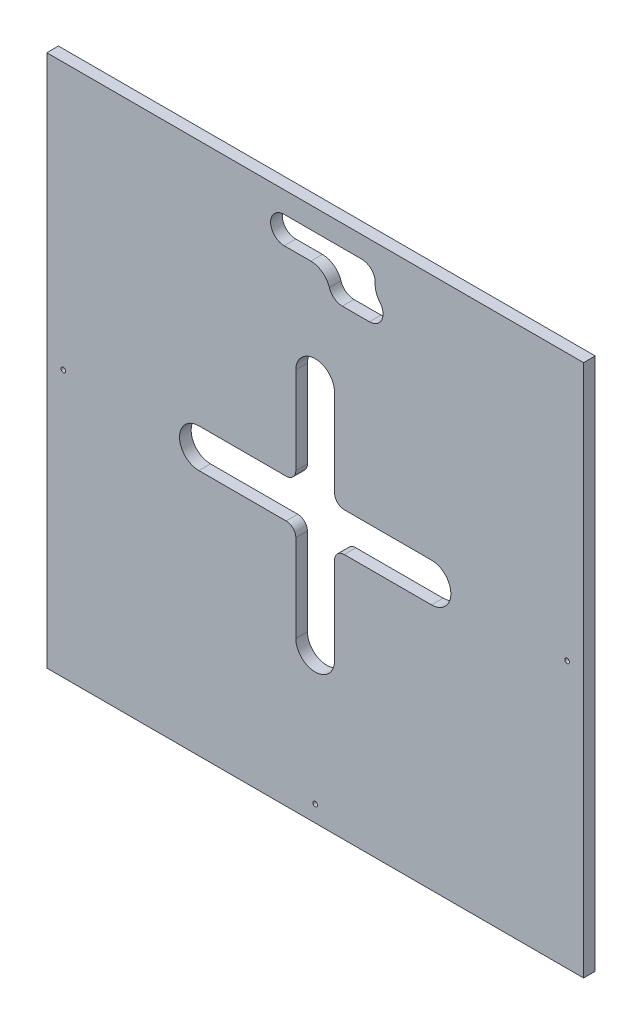
SolidWorks part; units mm, degrees
note: '?' marks a value the reader was unsure of. The reader was unsure of these and kept them because the rebuilt part matched: thickness of "Brida base1", "Chapa metálica12", "Chapa metálica15", "Chapa metálica16", "Chapa metálica17", "Chapa metálica18", "Chapa metálica19", "Chapa metálica20".
ref_plane "Alzado" through (0, 0, 0) normal (0, 0, 1) x (1, 0, 0)
ref_plane "Planta" through (0, 0, 0) normal (0, 1, 0) x (1, 0, 0)
ref_plane "Vista lateral" through (0, 0, 0) normal (1, 0, 0) x (0, 0, -1)
sketch "Croquis1" plane through (0, 0, 0) normal (0, 0, 1) x (1, 0, 0)
  line L1 (-138.5, 137.5) -> (138.5, 137.5)
  line L2 (-138.5, 137.5) -> (-138.5, -137.5)
  line L3 (-138.5, -137.5) -> (138.5, -137.5)
  line L4 (138.5, 137.5) -> (138.5, -137.5)
  line L5 (-138.5, 137.5) -> (138.5, -137.5) construction
  line L6 (-138.5, -137.5) -> (138.5, 137.5) construction
  point P0 (0, 0)
  dimension "D1" = 275
  dimension "D2" = 277
base flange "Brida base1" sketch "Croquis1" thickness 6 reverse thickness direction no parameters "D1"=0.7366
sketch "Croquis5" plane through (0, 0, -6) normal (0, 0, -1) x (-1, 0, 0)
  line L0 (122.5, 81.5) -> (122.5, 121.5) construction
  line L1 (115.5, 81.5) -> (115.5, 121.5)
  line L2 (129.5, 81.5) -> (129.5, 121.5)
  line L3 (138.5, 137.5) -> (138.5, -137.5) construction
  line L4 (110.5, 111.5) -> (110.5, 125.5) construction
  line L5 (103.5, 111.5) -> (103.5, 125.5)
  line L6 (117.5, 111.5) -> (117.5, 125.5)
  arc A0 (115.5, 81.5) -> (129.5, 81.5) centre (122.5, 81.5) ccw
  arc A1 (129.5, 121.5) -> (115.5, 121.5) centre (122.5, 121.5) ccw
  arc A2 (103.5, 111.5) -> (117.5, 111.5) centre (110.5, 111.5) ccw
  arc A3 (117.5, 125.5) -> (103.5, 125.5) centre (110.5, 125.5) ccw
  point P2 (122.5, 101.5)
  point P12 (110.5, 118.5)
  dimension "D2" = 7
  dimension "D5" = 7
  dimension "D1" = 16
  dimension "D3" = 40
  dimension "D4" = 36
  dimension "D6" = 12
  dimension "D7" = 17
  dimension "D8" = 14
extrude "Cortar-Extruir3" [suppressed] cut sketch "Croquis5" against normal through all both and the other way through all contours L6 A3 L5 A2 L1
fillet "Redondeo1" [suppressed] radius 10
sketch "Croquis6" plane through (0, 0, -6) normal (0, 0, -1) x (-1, 0, 0)
  line L0 (16, 119.5) -> (-24, 119.5) construction
  line L1 (16, 112.5) -> (-24, 112.5)
  line L2 (16, 126.5) -> (-24, 126.5)
  line L3 (-14, 107.5) -> (-28, 107.5) construction
  line L4 (-14, 100.5) -> (-28, 100.5)
  line L5 (-14, 114.5) -> (-28, 114.5)
  line L6 (-138.5, 137.5) -> (138.5, 137.5) construction
  arc A0 (16, 112.5) -> (16, 126.5) centre (16, 119.5) ccw
  arc A1 (-24, 126.5) -> (-24, 112.5) centre (-24, 119.5) ccw
  arc A2 (-14, 100.5) -> (-14, 114.5) centre (-14, 107.5) ccw
  arc A3 (-28, 114.5) -> (-28, 100.5) centre (-28, 107.5) ccw
  point P2 (-4, 119.5)
  point P9 (-21, 107.5)
  dimension "D1" = 40
  dimension "D3" = 7
  dimension "D4" = 7
  dimension "D2" = 14
  dimension "D5" = 17
  dimension "D6" = 12
  dimension "D7" = 18
  dimension "D8" = 4
extrude "Cortar-Extruir4" cut sketch "Croquis6" against normal blind 10 contours A3 L5 A2 L1 A0 L2 A1 | A1 A3 L4 A2 L1 | L5 A3 A1 L1 A2 normal cut yes
fillet "Redondeo2" radius 10 2 edges at (28.846, 114.4487, -3) (9.101, 112.5, -3)
sketch "Croquis7" plane through (0, 0, -6) normal (0, 0, -1) x (-1, 0, 0)
  line L0 (-138.5, 137.5) -> (138.5, 137.5) construction
  line L1 (-130, 129) -> (130, 129) construction
  line L2 (-130, 129) -> (-130, -129) construction
  line L3 (-130, -129) -> (130, -129) construction
  line L4 (130, 129) -> (130, -129) construction
  line L5 (-130, 129) -> (130, -129) construction
  line L6 (-130, -129) -> (130, 129) construction
  line L7 (138.5, 137.5) -> (138.5, -137.5) construction
  point P0 (0, 0)
  point P10 (-130, 0)
  point P11 (130, 0)
  point P12 (0, -129)
  dimension "D1" = 8.5
  dimension "D2" = 8.5
hole_wizard "Taladro de margen para M21" positions "Croquis11" profile "Croquis12" hole size "M2" standard "DIN" end condition through all
sketch "Croquis11" plane through (0, 0, -6) normal (0, 0, -1) x (-1, 0, 0)
  point P0 (-130, 0)
  point P3 (130, 0)
  point P6 (0, -129)
sketch "Croquis12" plane through (130, 0, -6) normal (1, 0, 0) x (0, 1, 0)
  line L0 (0, 0) -> (0, 6)
  line L1 (0, 6) -> (1.2, 6)
  line L2 (1.2, 6) -> (1.2, 0)
  line L5 (1.2, 0) -> (0, 0)
  line L11 (0, -6.35) -> (0, 107.95) construction
  dimension "Diámetro de taladro hasta el siguiente" = 2.4
  dimension "Profundidad de taladro hasta el siguiente" = 6
sketch "Croquis13" [suppressed] plane through (0, 0, 0) normal (0, 0, 1) x (1, 0, 0)
  line L1 (30, 126.5) -> (-30, 126.5) construction
  line L2 (30, 126.5) -> (30, -126.5) construction
  line L3 (30, -126.5) -> (-30, -126.5) construction
  line L4 (-30, 126.5) -> (-30, -126.5) construction
  line L5 (30, 126.5) -> (-30, -126.5) construction
  line L6 (30, -126.5) -> (-30, 126.5) construction
  line L7 (127.5, -30) -> (-127.5, -30) construction
  line L8 (127.5, -30) -> (127.5, 30) construction
  line L9 (127.5, 30) -> (-127.5, 30) construction
  line L10 (-127.5, -30) -> (-127.5, 30) construction
  line L11 (127.5, -30) -> (-127.5, 30) construction
  line L12 (127.5, 30) -> (-127.5, -30) construction
  point P0 (0, 0)
  point P5 (0, -126.5)
  point P6 (30, -126.5)
  point P8 (0, 126.5)
  point P9 (-30, -126.5)
  point P10 (-30, 126.5)
  point P11 (0, 0)
  point P12 (30, 126.5)
  point P18 (127.5, -30)
  point P19 (127.5, 30)
  point P20 (-127.5, 30)
  point P21 (-127.5, -30)
  dimension "D1" = 253
  dimension "D2" = 60
  dimension "D3" = 60
  dimension "D4" = 255
hole_wizard "Avellanado para tornillo con cabeza plana avellanada de M31" [suppressed] positions "Croquis14" profile "Croquis15" countersink size "M3" standard "DIN"
sketch "Croquis14" plane through (0, 0, 0) normal (0, 0, 1) x (1, 0, 0)
  point P0 (30, -126.5)
  point P6 (-30, -126.5)
  point P9 (-30, 126.5)
  point P15 (30, 126.5)
  point P19 (127.5, -30)
  point P22 (127.5, 30)
  point P25 (-127.5, -30)
  point P28 (-127.5, 30)
sketch "Croquis15" plane through (30, -126.5, 0) normal (1, 0, 0) x (0, -1, 0)
  line L0 (0, 0) -> (0, 6)
  line L1 (0, 6) -> (1.7, 6)
  line L2 (1.7, 6) -> (1.7, 1.45)
  line L3 (1.7, 1.45) -> (3.15, 0)
  line L5 (3.15, 0) -> (0, 0)
  line L6 (-1.7, 1.45) -> (-3.15, 0) construction
  line L11 (0, -6.35) -> (0, 107.95) construction
  dimension "Diámetro de taladro hasta el siguiente" = 3.4
  dimension "Profundidad de taladro hasta el siguiente" = 6
  dimension "Diámetro de avellanado cercano" = 6.3
  dimension "Ángulo de avellanado cercano" = 90
sketch "Croquis16" plane through (0, 0, -6) normal (0, 0, -1) x (-1, 0, 0)
  line L0 (0, 60) -> (0, -60) construction
  line L1 (10, 60) -> (10, -60)
  line L2 (-10, 60) -> (-10, -60)
  arc A0 (10, 60) -> (-10, 60) centre (0, 60) ccw
  arc A1 (-10, -60) -> (10, -60) centre (0, -60) ccw
  point P2 (0, 0)
  dimension "D2" = 10
  dimension "D1" = 120
extrude "Cortar-Extruir5" cut sketch "Croquis16" against normal through all normal cut yes
ref_axis "Eje1" through (0, 0, 0.3) along (0, 0, -1)?
pattern_circular "MatrizC1" count 4 over 360 about axis through (0, 0, 0) along (0, 0, 1) of "Cortar-Extruir5"
fillet "Redondeo3" radius 5 4 edges at (-10, -10, -3) (10, 10, -3) (10, -10, -3) (-10, 10, -3)
sketch "Líneas de pliegue1" [suppressed] plane through (0, 0, 0) normal (0, 1, 0) x (1, 0, 0)
sketch "Cuadro delimitador1" [suppressed] plane through (0, 0, 0) normal (0, 1, 0) x (1, 0, 0)
sheet metal parameters "Chapa metálica12" thickness 6 parameters "D1"=0.7366, "D7"=3
flat pattern "Chapa desplegada12" [suppressed]
sketch "Líneas de pliegue2" plane through (0, 0, 0) normal (0, 1, 0) x (1, 0, 0)
sketch3d "Cuadro delimitador2" [suppressed]
  line L0 (-138.5, -137.5, 0) -> (138.5, -137.5, 0) construction
  line L1 (-138.5, 137.5, 0) -> (138.5, 137.5, 0) construction
  line L2 (-138.5, -137.5, 0) -> (-138.5, 137.5, 0) construction
  line L3 (138.5, -137.5, 0) -> (138.5, 137.5, 0) construction
sketch "Croquis7-1" [suppressed] plane through (0, 0, -6) normal (0, 0, -1) x (-1, 0, 0)
  line L0 (-138.5, 137.5) -> (138.5, 137.5)
  line L1 (-130, 129) -> (130, 129) construction
  line L2 (-130, 129) -> (-130, -129) construction
  line L3 (-130, -129) -> (130, -129) construction
  line L4 (130, 129) -> (130, -129) construction
  line L5 (-130, 129) -> (130, -129) construction
  line L6 (-130, -129) -> (130, 129) construction
  line L7 (138.5, 137.5) -> (138.5, -137.5)
  point P0 (0, 0)
  point P10 (-130, 0)
  point P11 (130, 0)
  point P12 (0, -129)
  dimension "D1" = 8.5
  dimension "D2" = 8.5
sketch "Croquis7-7" [suppressed] plane through (0, 0, -6) normal (0, 0, -1) x (-1, 0, 0)
  line L0 (-138.5, 137.5) -> (138.5, 137.5)
  line L1 (-130, 129) -> (130, 129) construction
  line L2 (-130, 129) -> (-130, -129) construction
  line L3 (-130, -129) -> (130, -129) construction
  line L4 (130, 129) -> (130, -129) construction
  line L5 (-130, 129) -> (130, -129) construction
  line L6 (-130, -129) -> (130, 129) construction
  line L7 (138.5, 137.5) -> (138.5, -137.5)
  point P0 (0, 0)
  point P10 (-130, 0)
  point P11 (130, 0)
  point P12 (0, -129)
  dimension "D1" = 8.5
  dimension "D2" = 8.5
sheet metal parameters "Chapa metálica15" thickness 6 parameters "D1"=0.7366, "D7"=3
flat pattern "Chapa desplegada12"
sketch "Líneas de pliegue2" plane through (0, 0, 0) normal (0, 1, 0) x (1, 0, 0)
sketch3d "Cuadro delimitador2" [suppressed]
  line L0 (135.5, 137.5, 0) -> (135.5, -137.5, 0) construction
  line L1 (-135.5, 137.5, 0) -> (-135.5, -137.5, 0) construction
  line L2 (135.5, 137.5, 0) -> (-135.5, 137.5, 0) construction
  line L3 (135.5, -137.5, 0) -> (-135.5, -137.5, 0) construction
sheet metal parameters "Chapa metálica16" thickness 6 parameters "D1"=0.7366, "D7"=3
flat pattern "Chapa desplegada12" [suppressed]
sketch "Líneas de pliegue2" plane through (0, 0, 0) normal (0, 1, 0) x (1, 0, 0)
sketch3d "Cuadro delimitador2" [suppressed]
  line L0 (-138.5, -137.5, 0) -> (138.5, -137.5, 0) construction
  line L1 (-138.5, 137.5, 0) -> (138.5, 137.5, 0) construction
  line L2 (-138.5, -137.5, 0) -> (-138.5, 137.5, 0) construction
  line L3 (138.5, -137.5, 0) -> (138.5, 137.5, 0) construction
sketch "Croquis7-3" plane through (0, 0, -6) normal (0, 0, -1) x (-1, 0, 0)
  line L0 (-138.5, 137.5) -> (138.5, 137.5)
  line L1 (-125, 124) -> (125, 124) construction
  line L2 (-125, 124) -> (-125, -124) construction
  line L3 (-125, -124) -> (125, -124) construction
  line L4 (125, 124) -> (125, -124) construction
  line L5 (-125, 124) -> (125, -124) construction
  line L6 (-125, -124) -> (125, 124) construction
  line L7 (138.5, 137.5) -> (138.5, -137.5)
  point P0 (0, 0)
  point P10 (-125, 0)
  point P11 (125, 0)
  point P12 (0, -124)
  dimension "D1" = 13.5
  dimension "D2" = 13.5
sketch "Croquis7-4" plane through (0, 0, -6) normal (0, 0, -1) x (-1, 0, 0)
  line L0 (-138.5, 137.5) -> (138.5, 137.5)
  line L1 (-125, 124) -> (125, 124) construction
  line L2 (-125, 124) -> (-125, -124) construction
  line L3 (-125, -124) -> (125, -124) construction
  line L4 (125, 124) -> (125, -124) construction
  line L5 (-125, 124) -> (125, -124) construction
  line L6 (-125, -124) -> (125, 124) construction
  line L7 (138.5, 137.5) -> (138.5, -137.5)
  point P0 (0, 0)
  point P10 (-125, 0)
  point P11 (125, 0)
  point P12 (0, -124)
  dimension "D1" = 13.5
  dimension "D2" = 13.5
sheet metal parameters "Chapa metálica17" thickness 6 parameters "D1"=0.7366, "D7"=3
flat pattern "Chapa desplegada12" [suppressed]
sketch "Líneas de pliegue2" plane through (0, 0, 0) normal (0, 1, 0) x (1, 0, 0)
sketch3d "Cuadro delimitador2" [suppressed]
  line L0 (-138.5, -137.5, 0) -> (138.5, -137.5, 0) construction
  line L1 (-138.5, 137.5, 0) -> (138.5, 137.5, 0) construction
  line L2 (-138.5, -137.5, 0) -> (-138.5, 137.5, 0) construction
  line L3 (138.5, -137.5, 0) -> (138.5, 137.5, 0) construction
sketch "Croquis7-1" plane through (0, 0, -6) normal (0, 0, -1) x (-1, 0, 0)
  line L0 (-138.5, 137.5) -> (138.5, 137.5) construction
  line L1 (-130, 129) -> (130, 129) construction
  line L2 (-130, 129) -> (-130, -129) construction
  line L3 (-130, -129) -> (130, -129) construction
  line L4 (130, 129) -> (130, -129) construction
  line L5 (-130, 129) -> (130, -129) construction
  line L6 (-130, -129) -> (130, 129) construction
  line L7 (138.5, 137.5) -> (138.5, -137.5) construction
  point P0 (0, 0)
  point P10 (-130, 0)
  point P11 (130, 0)
  point P12 (0, -129)
  dimension "D1" = 8.5
  dimension "D2" = 8.5
sketch "Croquis7-2" plane through (0, 0, -6) normal (0, 0, -1) x (-1, 0, 0)
  line L0 (-138.5, 137.5) -> (138.5, 137.5)
  line L1 (-131, 130) -> (131, 130) construction
  line L2 (-131, 130) -> (-131, -130) construction
  line L3 (-131, -130) -> (131, -130) construction
  line L4 (131, 130) -> (131, -130) construction
  line L5 (-131, 130) -> (131, -130) construction
  line L6 (-131, -130) -> (131, 130) construction
  line L7 (138.5, 137.5) -> (138.5, -137.5)
  point P0 (0, 0)
  point P10 (-131, 0)
  point P11 (131, 0)
  point P12 (0, -130)
  dimension "D1" = 7.5
  dimension "D2" = 7.5
sketch "Croquis7-5" plane through (0, 0, -6) normal (0, 0, -1) x (-1, 0, 0)
  line L0 (-138.5, 137.5) -> (138.5, 137.5)
  line L1 (-125, 124) -> (125, 124) construction
  line L2 (-125, 124) -> (-125, -124) construction
  line L3 (-125, -124) -> (125, -124) construction
  line L4 (125, 124) -> (125, -124) construction
  line L5 (-125, 124) -> (125, -124) construction
  line L6 (-125, -124) -> (125, 124) construction
  line L7 (138.5, 137.5) -> (138.5, -137.5)
  point P0 (0, 0)
  point P10 (-125, 0)
  point P11 (125, 0)
  point P12 (0, -124)
  dimension "D1" = 13.5
  dimension "D2" = 13.5
sketch "Croquis7-6" plane through (0, 0, -6) normal (0, 0, -1) x (-1, 0, 0)
  line L0 (-138.5, 137.5) -> (138.5, 137.5)
  line L1 (-130, 129) -> (130, 129) construction
  line L2 (-130, 129) -> (-130, -129) construction
  line L3 (-130, -129) -> (130, -129) construction
  line L4 (130, 129) -> (130, -129) construction
  line L5 (-130, 129) -> (130, -129) construction
  line L6 (-130, -129) -> (130, 129) construction
  line L7 (138.5, 137.5) -> (138.5, -137.5)
  point P0 (0, 0)
  point P10 (-130, 0)
  point P11 (130, 0)
  point P12 (0, -129)
  dimension "D1" = 8.5
  dimension "D2" = 8.5
sketch "Croquis7-10" plane through (0, 0, -6) normal (0, 0, -1) x (-1, 0, 0)
  line L0 (-138.5, 137.5) -> (138.5, 137.5) construction
  line L1 (-130, 129) -> (130, 129) construction
  line L2 (-130, 129) -> (-130, -129) construction
  line L3 (-130, -129) -> (130, -129) construction
  line L4 (130, 129) -> (130, -129) construction
  line L5 (-130, 129) -> (130, -129) construction
  line L6 (-130, -129) -> (130, 129) construction
  line L7 (138.5, 137.5) -> (138.5, -137.5) construction
  point P0 (0, 0)
  point P10 (-130, 0)
  point P11 (130, 0)
  point P12 (0, -129)
  dimension "D1" = 8.5
  dimension "D2" = 8.5
sheet metal parameters "Chapa metálica18" [suppressed] thickness 6 parameters "D1"=0.7366, "D7"=3
flat pattern "Chapa desplegada12" [suppressed]
sketch "Líneas de pliegue2" plane through (0, 0, 0) normal (0, 1, 0) x (1, 0, 0)
sketch3d "Cuadro delimitador2" [suppressed]
  line L0 (-138.5, -137.5, 0) -> (138.5, -137.5, 0) construction
  line L1 (-138.5, 137.5, 0) -> (138.5, 137.5, 0) construction
  line L2 (-138.5, -137.5, 0) -> (-138.5, 137.5, 0) construction
  line L3 (138.5, -137.5, 0) -> (138.5, 137.5, 0) construction
sketch "Croquis7-1" [suppressed] plane through (0, 0, -6) normal (0, 0, -1) x (-1, 0, 0)
  line L0 (-138.5, 137.5) -> (138.5, 137.5)
  line L1 (-130, 129) -> (130, 129) construction
  line L2 (-130, 129) -> (-130, -129) construction
  line L3 (-130, -129) -> (130, -129) construction
  line L4 (130, 129) -> (130, -129) construction
  line L5 (-130, 129) -> (130, -129) construction
  line L6 (-130, -129) -> (130, 129) construction
  line L7 (138.5, 137.5) -> (138.5, -137.5)
  point P0 (0, 0)
  point P10 (-130, 0)
  point P11 (130, 0)
  point P12 (0, -129)
  dimension "D1" = 8.5
  dimension "D2" = 8.5
sketch "Croquis7-7" [suppressed] plane through (0, 0, -6) normal (0, 0, -1) x (-1, 0, 0)
  line L0 (-138.5, 137.5) -> (138.5, 137.5)
  line L1 (-130, 129) -> (130, 129) construction
  line L2 (-130, 129) -> (-130, -129) construction
  line L3 (-130, -129) -> (130, -129) construction
  line L4 (130, 129) -> (130, -129) construction
  line L5 (-130, 129) -> (130, -129) construction
  line L6 (-130, -129) -> (130, 129) construction
  line L7 (138.5, 137.5) -> (138.5, -137.5)
  point P0 (0, 0)
  point P10 (-130, 0)
  point P11 (130, 0)
  point P12 (0, -129)
  dimension "D1" = 8.5
  dimension "D2" = 8.5
sketch "Croquis7-8" [suppressed] plane through (0, 0, -6) normal (0, 0, -1) x (-1, 0, 0)
  line L0 (-138.5, 137.5) -> (138.5, 137.5)
  line L1 (-130, 129) -> (130, 129) construction
  line L2 (-130, 129) -> (-130, -129) construction
  line L3 (-130, -129) -> (130, -129) construction
  line L4 (130, 129) -> (130, -129) construction
  line L5 (-130, 129) -> (130, -129) construction
  line L6 (-130, -129) -> (130, 129) construction
  line L7 (138.5, 137.5) -> (138.5, -137.5)
  point P0 (0, 0)
  point P10 (-130, 0)
  point P11 (130, 0)
  point P12 (0, -129)
  dimension "D1" = 8.5
  dimension "D2" = 8.5
sketch "Croquis7-9" [suppressed] plane through (0, 0, -6) normal (0, 0, -1) x (-1, 0, 0)
  line L0 (-138.5, 137.5) -> (138.5, 137.5)
  line L1 (-130, 129) -> (130, 129) construction
  line L2 (-130, 129) -> (-130, -129) construction
  line L3 (-130, -129) -> (130, -129) construction
  line L4 (130, 129) -> (130, -129) construction
  line L5 (-130, 129) -> (130, -129) construction
  line L6 (-130, -129) -> (130, 129) construction
  line L7 (138.5, 137.5) -> (138.5, -137.5)
  point P0 (0, 0)
  point P10 (-130, 0)
  point P11 (130, 0)
  point P12 (0, -129)
  dimension "D1" = 8.5
  dimension "D2" = 8.5
sheet metal parameters "Chapa metálica19" thickness 6 parameters "D1"=0.7366, "D7"=3
flat pattern "Chapa desplegada12" [suppressed]
sketch "Líneas de pliegue2" plane through (0, 0, 0) normal (0, 1, 0) x (1, 0, 0)
sketch3d "Cuadro delimitador2" [suppressed]
  line L0 (-138.5, -137.5, 0) -> (138.5, -137.5, 0) construction
  line L1 (-138.5, 137.5, 0) -> (138.5, 137.5, 0) construction
  line L2 (-138.5, -137.5, 0) -> (-138.5, 137.5, 0) construction
  line L3 (138.5, -137.5, 0) -> (138.5, 137.5, 0) construction
sketch "Croquis7-1" plane through (0, 0, -6) normal (0, 0, -1) x (-1, 0, 0)
  line L0 (-138.5, 137.5) -> (138.5, 137.5) construction
  line L1 (-130, 129) -> (130, 129) construction
  line L2 (-130, 129) -> (-130, -129) construction
  line L3 (-130, -129) -> (130, -129) construction
  line L4 (130, 129) -> (130, -129) construction
  line L5 (-130, 129) -> (130, -129) construction
  line L6 (-130, -129) -> (130, 129) construction
  line L7 (138.5, 137.5) -> (138.5, -137.5) construction
  point P0 (0, 0)
  point P10 (-130, 0)
  point P11 (130, 0)
  point P12 (0, -129)
  dimension "D1" = 8.5
  dimension "D2" = 8.5
sketch "Croquis7-2" plane through (0, 0, -6) normal (0, 0, -1) x (-1, 0, 0)
  line L0 (-138.5, 137.5) -> (138.5, 137.5)
  line L1 (-131, 130) -> (131, 130) construction
  line L2 (-131, 130) -> (-131, -130) construction
  line L3 (-131, -130) -> (131, -130) construction
  line L4 (131, 130) -> (131, -130) construction
  line L5 (-131, 130) -> (131, -130) construction
  line L6 (-131, -130) -> (131, 130) construction
  line L7 (138.5, 137.5) -> (138.5, -137.5)
  point P0 (0, 0)
  point P10 (-131, 0)
  point P11 (131, 0)
  point P12 (0, -130)
  dimension "D1" = 7.5
  dimension "D2" = 7.5
sketch "Croquis7-5" plane through (0, 0, -6) normal (0, 0, -1) x (-1, 0, 0)
  line L0 (-138.5, 137.5) -> (138.5, 137.5)
  line L1 (-125, 124) -> (125, 124) construction
  line L2 (-125, 124) -> (-125, -124) construction
  line L3 (-125, -124) -> (125, -124) construction
  line L4 (125, 124) -> (125, -124) construction
  line L5 (-125, 124) -> (125, -124) construction
  line L6 (-125, -124) -> (125, 124) construction
  line L7 (138.5, 137.5) -> (138.5, -137.5)
  point P0 (0, 0)
  point P10 (-125, 0)
  point P11 (125, 0)
  point P12 (0, -124)
  dimension "D1" = 13.5
  dimension "D2" = 13.5
sketch "Croquis7-6" plane through (0, 0, -6) normal (0, 0, -1) x (-1, 0, 0)
  line L0 (-138.5, 137.5) -> (138.5, 137.5)
  line L1 (-130, 129) -> (130, 129) construction
  line L2 (-130, 129) -> (-130, -129) construction
  line L3 (-130, -129) -> (130, -129) construction
  line L4 (130, 129) -> (130, -129) construction
  line L5 (-130, 129) -> (130, -129) construction
  line L6 (-130, -129) -> (130, 129) construction
  line L7 (138.5, 137.5) -> (138.5, -137.5)
  point P0 (0, 0)
  point P10 (-130, 0)
  point P11 (130, 0)
  point P12 (0, -129)
  dimension "D1" = 8.5
  dimension "D2" = 8.5
sketch "Croquis7-10" plane through (0, 0, -6) normal (0, 0, -1) x (-1, 0, 0)
  line L0 (-138.5, 137.5) -> (138.5, 137.5)
  line L1 (-130, 129) -> (130, 129) construction
  line L2 (-130, 129) -> (-130, -129) construction
  line L3 (-130, -129) -> (130, -129) construction
  line L4 (130, 129) -> (130, -129) construction
  line L5 (-130, 129) -> (130, -129) construction
  line L6 (-130, -129) -> (130, 129) construction
  line L7 (138.5, 137.5) -> (138.5, -137.5)
  point P0 (0, 0)
  point P10 (-130, 0)
  point P11 (130, 0)
  point P12 (0, -129)
  dimension "D1" = 8.5
  dimension "D2" = 8.5
sketch "Croquis7-11" plane through (0, 0, -6) normal (0, 0, -1) x (-1, 0, 0)
  line L0 (-138.5, 137.5) -> (138.5, 137.5) construction
  line L1 (-130, 129) -> (130, 129) construction
  line L2 (-130, 129) -> (-130, -129) construction
  line L3 (-130, -129) -> (130, -129) construction
  line L4 (130, 129) -> (130, -129) construction
  line L5 (-130, 129) -> (130, -129) construction
  line L6 (-130, -129) -> (130, 129) construction
  line L7 (138.5, 137.5) -> (138.5, -137.5) construction
  point P0 (0, 0)
  point P10 (-130, 0)
  point P11 (130, 0)
  point P12 (0, -129)
  dimension "D1" = 8.5
  dimension "D2" = 8.5
sheet metal parameters "Chapa metálica20" thickness 6 parameters "D1"=0.7366, "D7"=3
flat pattern "Chapa desplegada12" [suppressed]
sketch "Líneas de pliegue2" plane through (0, 0, 0) normal (0, 1, 0) x (1, 0, 0)
sketch3d "Cuadro delimitador2" [suppressed]
  line L0 (-138.5, -137.5, 0) -> (138.5, -137.5, 0) construction
  line L1 (-138.5, 137.5, 0) -> (138.5, 137.5, 0) construction
  line L2 (-138.5, -137.5, 0) -> (-138.5, 137.5, 0) construction
  line L3 (138.5, -137.5, 0) -> (138.5, 137.5, 0) construction
sketch "Croquis7-1" plane through (0, 0, -6) normal (0, 0, -1) x (-1, 0, 0)
  line L0 (-138.5, 137.5) -> (138.5, 137.5) construction
  line L1 (-130, 129) -> (130, 129) construction
  line L2 (-130, 129) -> (-130, -129) construction
  line L3 (-130, -129) -> (130, -129) construction
  line L4 (130, 129) -> (130, -129) construction
  line L5 (-130, 129) -> (130, -129) construction
  line L6 (-130, -129) -> (130, 129) construction
  line L7 (138.5, 137.5) -> (138.5, -137.5) construction
  point P0 (0, 0)
  point P10 (-130, 0)
  point P11 (130, 0)
  point P12 (0, -129)
  dimension "D1" = 8.5
  dimension "D2" = 8.5
sketch "Croquis7-2" plane through (0, 0, -6) normal (0, 0, -1) x (-1, 0, 0)
  line L0 (-138.5, 137.5) -> (138.5, 137.5)
  line L1 (-131, 130) -> (131, 130) construction
  line L2 (-131, 130) -> (-131, -130) construction
  line L3 (-131, -130) -> (131, -130) construction
  line L4 (131, 130) -> (131, -130) construction
  line L5 (-131, 130) -> (131, -130) construction
  line L6 (-131, -130) -> (131, 130) construction
  line L7 (138.5, 137.5) -> (138.5, -137.5)
  point P0 (0, 0)
  point P10 (-131, 0)
  point P11 (131, 0)
  point P12 (0, -130)
  dimension "D1" = 7.5
  dimension "D2" = 7.5
sketch "Croquis7-5" plane through (0, 0, -6) normal (0, 0, -1) x (-1, 0, 0)
  line L0 (-138.5, 137.5) -> (138.5, 137.5)
  line L1 (-125, 124) -> (125, 124) construction
  line L2 (-125, 124) -> (-125, -124) construction
  line L3 (-125, -124) -> (125, -124) construction
  line L4 (125, 124) -> (125, -124) construction
  line L5 (-125, 124) -> (125, -124) construction
  line L6 (-125, -124) -> (125, 124) construction
  line L7 (138.5, 137.5) -> (138.5, -137.5)
  point P0 (0, 0)
  point P10 (-125, 0)
  point P11 (125, 0)
  point P12 (0, -124)
  dimension "D1" = 13.5
  dimension "D2" = 13.5
sketch "Croquis7-6" plane through (0, 0, -6) normal (0, 0, -1) x (-1, 0, 0)
  line L0 (-138.5, 137.5) -> (138.5, 137.5)
  line L1 (-130, 129) -> (130, 129) construction
  line L2 (-130, 129) -> (-130, -129) construction
  line L3 (-130, -129) -> (130, -129) construction
  line L4 (130, 129) -> (130, -129) construction
  line L5 (-130, 129) -> (130, -129) construction
  line L6 (-130, -129) -> (130, 129) construction
  line L7 (138.5, 137.5) -> (138.5, -137.5)
  point P0 (0, 0)
  point P10 (-130, 0)
  point P11 (130, 0)
  point P12 (0, -129)
  dimension "D1" = 8.5
  dimension "D2" = 8.5
sketch "Croquis7-10" plane through (0, 0, -6) normal (0, 0, -1) x (-1, 0, 0)
  line L0 (-138.5, 137.5) -> (138.5, 137.5)
  line L1 (-130, 129) -> (130, 129) construction
  line L2 (-130, 129) -> (-130, -129) construction
  line L3 (-130, -129) -> (130, -129) construction
  line L4 (130, 129) -> (130, -129) construction
  line L5 (-130, 129) -> (130, -129) construction
  line L6 (-130, -129) -> (130, 129) construction
  line L7 (138.5, 137.5) -> (138.5, -137.5)
  point P0 (0, 0)
  point P10 (-130, 0)
  point P11 (130, 0)
  point P12 (0, -129)
  dimension "D1" = 8.5
  dimension "D2" = 8.5
sketch "Croquis7-11" plane through (0, 0, -6) normal (0, 0, -1) x (-1, 0, 0)
  line L0 (-138.5, 137.5) -> (138.5, 137.5)
  line L1 (-130, 129) -> (130, 129) construction
  line L2 (-130, 129) -> (-130, -129) construction
  line L3 (-130, -129) -> (130, -129) construction
  line L4 (130, 129) -> (130, -129) construction
  line L5 (-130, 129) -> (130, -129) construction
  line L6 (-130, -129) -> (130, 129) construction
  line L7 (138.5, 137.5) -> (138.5, -137.5)
  point P0 (0, 0)
  point P10 (-130, 0)
  point P11 (130, 0)
  point P12 (0, -129)
  dimension "D1" = 8.5
  dimension "D2" = 8.5
sketch "Croquis7-12" plane through (0, 0, -6) normal (0, 0, -1) x (-1, 0, 0)
  line L0 (-138.5, 137.5) -> (138.5, 137.5) construction
  line L1 (-130, 129) -> (130, 129) construction
  line L2 (-130, 129) -> (-130, -129) construction
  line L3 (-130, -129) -> (130, -129) construction
  line L4 (130, 129) -> (130, -129) construction
  line L5 (-130, 129) -> (130, -129) construction
  line L6 (-130, -129) -> (130, 129) construction
  line L7 (138.5, 137.5) -> (138.5, -137.5) construction
  point P0 (0, 0)
  point P10 (-130, 0)
  point P11 (130, 0)
  point P12 (0, -129)
  dimension "D1" = 8.5
  dimension "D2" = 8.5
